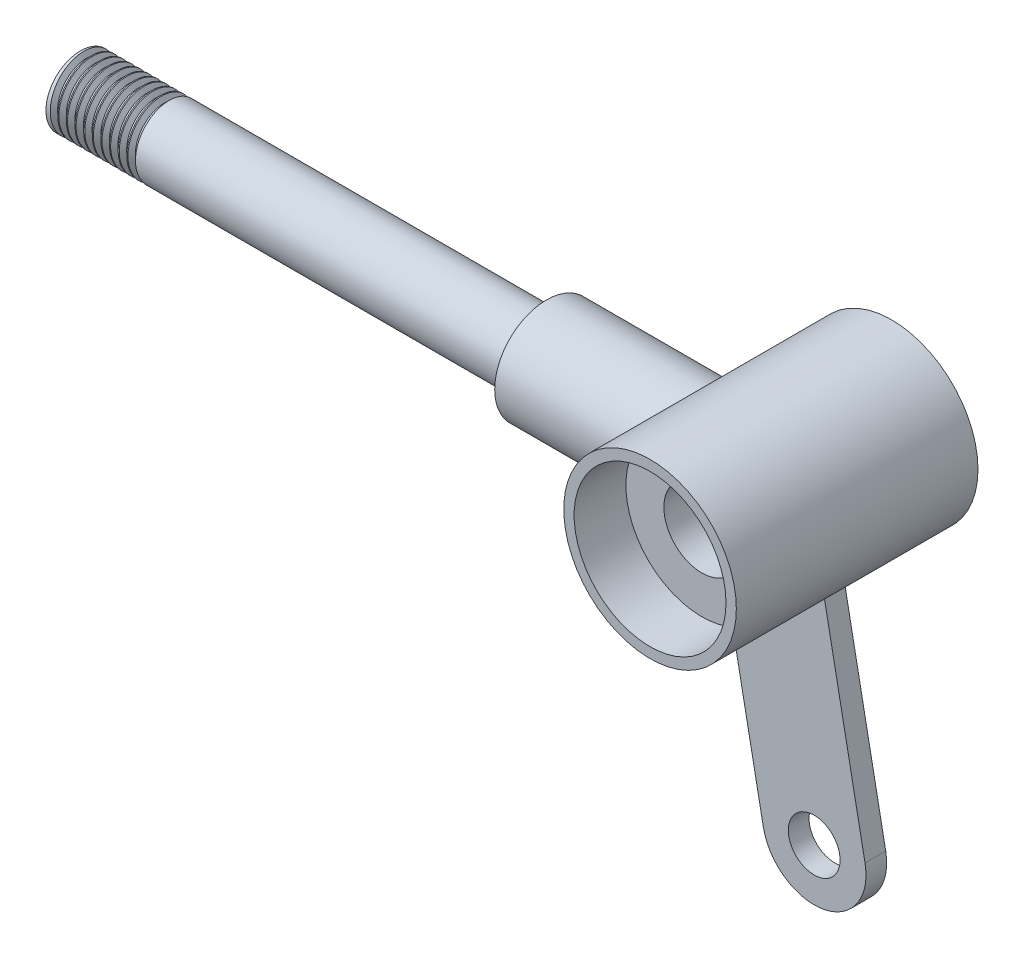
SolidWorks part; units mm, degrees
ref_plane "Płaszczyzna przednia" through (0, 0, 0) normal (0, 0, 1) x (1, 0, 0)
ref_plane "Płaszczyzna górna" through (0, 0, 0) normal (0, 1, 0) x (1, 0, 0)
ref_plane "Płaszczyzna prawa" through (0, 0, 0) normal (1, 0, 0) x (0, 0, -1)
sketch "Szkic1" plane through (0, 0, 0) normal (0, 1, 0) x (1, 0, 0)
  line L0 (0, 0) -> (0, 70) construction
  line L2 (-11, 70) -> (-25, 70)
  line L3 (-11, 70) -> (-11, 0)
  line L4 (-11, 0) -> (-25, 0)
  line L5 (-25, 70) -> (-25, 0)
  line L6 (-11, 70) -> (-22, 70)
  line L7 (-11, 70) -> (-11, 55)
  line L8 (-11, 55) -> (-22, 55)
  line L9 (-22, 70) -> (-22, 55)
  line L10 (-11, 0) -> (-22, 0)
  line L11 (-11, 0) -> (-11, 15)
  line L12 (-11, 15) -> (-22, 15)
  line L13 (-22, 0) -> (-22, 15)
  dimension "D1" = 70
  dimension "D2" = 50
  dimension "D3" = 22
  dimension "D4" = 44
  dimension "D5" = 44
  dimension "D6" = 15
  dimension "D7" = 15
revolve "Obrót1" add sketch "Szkic1" angle 360 about L0 region at (-18.7615, 0, -35)
ref_plane "Płaszczyzna1" through (-25, 0, 0) normal (-1, 0, 0) x (0, 0, 1)
sketch "Szkic2" plane through (-25, 0, 0) normal (-1, 0, 0) x (0, 0, 1)
  line L0 (-70, 0) -> (0, 0) construction
  line L1 (-70, 25) -> (-70, -25) construction
  circle A0 centre (-35, 0) radius 15
  dimension "D1" = 30
extrude "Dodanie-wyciągnięcie1" add sketch "Szkic2" along normal blind 40 and the other way up to surface other way up to face at (25, 0, 0)
ref_plane "Płaszczyzna2" through (0, 0, -35) normal (0, 0, 1) x (1, 0, 0)
sketch "Szkic3" plane through (0, 0, -35) normal (0, 0, 1) x (1, 0, 0)
  line L0 (0, 0) -> (0, -96.5374) construction
  line L1 (0, 0) -> (15.5504, -80) construction
  line L2 (0, 0) -> (15.5504, -80) construction
  line L3 (14.7244, 2.8621) -> (30.2748, -77.1379)
  line L4 (-14.7244, -2.8621) -> (0.826, -82.8621)
  arc A0 (14.7244, 2.8621) -> (-14.7244, -2.8621) centre (0, 0) ccw
  arc A1 (0.826, -82.8621) -> (30.2748, -77.1379) centre (15.5504, -80) ccw
  circle A2 centre (0, 0) radius 20
  point P3 (7.7752, -40)
  dimension "D2" = 15
  dimension "D3" = 40
  dimension "D1" = 11
  dimension "D4" = 80
extrude "Dodanie-wyciągnięcie2" add sketch "Szkic3" along normal blind 3 and the other way blind 3 contours A2 L4 A1 L3 region at (10.6184, -54.6268, -35)
sketch "Szkic4" plane through (0, 0, -32) normal (0, 0, 1) x (1, 0, 0)
  line L0 (0.826, -82.8621) -> (30.2748, -77.1379) construction
  circle A0 centre (15.5504, -80) radius 7.5
  point P8 (15.5504, -80)
  dimension "D1" = 15
extrude "Wytnij-wyciągnięcie1" cut sketch "Szkic4" against normal up to next contours A0
sketch "Szkic6" plane through (-65, 0, 0) normal (-1, 0, 0) x (0, 0, 1)
  circle A0 centre (-35, 0) radius 10
  circle A1 centre (-35, 0) radius 15 construction
  dimension "D1" = 20
extrude "Dodanie-wyciągnięcie3" add sketch "Szkic6" along normal blind 135
thread "Gwint1" pitch 2.5 method cut profile "Profil gwintu1" start angle 0, offset 0, length 25, pitch 2.5, diameter 20
ref_plane "Płaszczyzna3" through (-200, 0, -45) normal (0, -1, 0) x (0, 0, -1)
sketch "Profil gwintu1" plane through (-200, 0, -45) normal (0, -1, 0) x (0, 0, -1)
  line L0 (0, 0) -> (0, 2.5) construction
  line L11 (0, 0) -> (0, 2.1875)
  line L12 (0, 2.1875) -> (-1.3532, 1.4062)
  line L13 (-1.3532, 1.4062) -> (-1.3532, 0.7812)
  line L15 (-1.3532, 0.7812) -> (0, 0)
  line L17 (-1.3532, 1.0937) -> (0, 1.0937) construction
  point P2 (0, 0)
  dimension "Pitch" = 2.5
  dimension "Profile_Angle" = 60
  dimension "Profile_Land" = 0.625
  dimension "Profile_Height" = 1.3532
